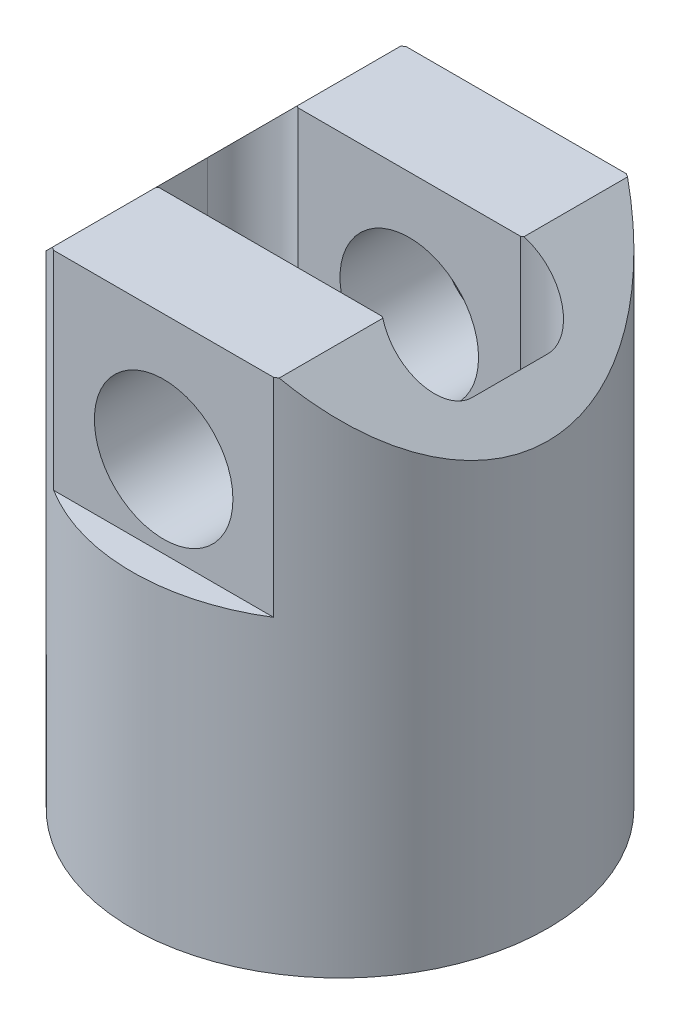
SolidWorks part; units mm, degrees
material "Простая углеродистая сталь"
ref_plane "Спереди" through (0, 0, 0) normal (0, 0, 1) x (1, 0, 0)
ref_plane "Сверху" through (0, 0, 0) normal (0, 1, 0) x (1, 0, 0)
ref_plane "Справа" through (0, 0, 0) normal (1, 0, 0) x (0, 0, -1)
sketch "Эскиз1" plane through (0, 0, 0) normal (0, 0, 1) x (1, 0, 0)
  line L0 (0, 0) -> (0, 118.6898) construction
  line L2 (-33, 0) -> (-33, 82)
  line L3 (-33, 82) -> (0, 82)
  line L4 (0, 82) -> (0, 40)
  line L5 (0, 40) -> (-22.5, 40)
  line L6 (-22.5, 40) -> (-22.5, 37)
  line L7 (-22.5, 37) -> (-27.25, 37)
  line L8 (-28.25, 36) -> (-28.25, 29.4142)
  line L9 (-27.9571, 28.7071) -> (0, 0.75)
  line L10 (0, 0.75) -> (0, 0)
  line L11 (0, 0) -> (-33, 0)
  arc A0 (-28.25, 29.4142) -> (-27.9571, 28.7071) centre (-27.25, 29.4142) ccw
  arc A1 (-27.25, 37) -> (-28.25, 36) centre (-27.25, 36) ccw
  point P14 (-28.25, 29)
  point P17 (-28.25, 37)
  dimension "D9" = 1
  dimension "D1" = 66
  dimension "H" = 82
  dimension "D3" = 45
  dimension "D4" = 56.5
  dimension "D7" = 8
  dimension "D8" = 45
  dimension "h1" = 40
  dimension "h2" = 37
revolve "Повернуть1" add sketch "Эскиз1" angle 360 about L0
hole_wizard "Отверстие обработанное метчиком M561" positions "Эскиз3" profile "Эскиз2" tap size "M56" standard "ISO"
sketch "Эскиз3" plane through (0, 0, 0) normal (0, -1, 0) x (-1, 0, 0)
  point P0 (0, 0)
sketch "Эскиз2" plane through (0, 0, 0) normal (1, 0, 0) x (0, 0, -1)
  line L0 (0, 0) -> (0, 30)
  line L1 (0, 30) -> (27, 30)
  line L2 (27, 30) -> (27, 2)
  line L3 (27, 2) -> (29, 0)
  line L5 (29, 0) -> (0, 0)
  line L6 (-27, 2) -> (-29, 0) construction
  line L10 (0, 30) -> (-27, 30) construction
  line L11 (0, -6.35) -> (0, 107.95) construction
  dimension "Диаметр сверла" = 54
  dimension "Глубина сверла" = 30
  dimension "Диаметр передней зенковки" = 58
  dimension "Угол передней зенковки" = 90
  dimension "Угол заточки сверла" = 180
cosmetic thread "Отверстие резьбы2" parameters "D1"=27.75, "D2"=56
sketch "Эскиз4" plane through (0, 0, 0) normal (0, 0, 1) x (1, 0, 0)
  line L0 (33, 82) -> (-33, 82) construction
  line L1 (-33, 49) -> (33, 49)
  line L2 (-33, 49) -> (-33, 82)
  line L3 (-33, 82) -> (33, 82)
  line L4 (33, 49) -> (33, 82)
  line L5 (33, 0) -> (33, 82) construction
  line L6 (-33, 82) -> (-33, 0) construction
  dimension "D1" = 33
extrude "Вырез-Вытянуть1" cut sketch "Эскиз4" along normal through all from offset 28
extrude "Вырез-Вытянуть2" cut sketch "Эскиз4<2>" against normal through all from offset 28 offset against normal yes
sketch "Эскиз4<2>" plane through (0, 0, 0) normal (0, 0, 1) x (1, 0, 0) same geometry as "Эскиз4"
sketch "Эскиз5" plane through (0, 0, 28) normal (0, 0, 1) x (1, 0, 0)
  circle A0 centre (0, 62) radius 11
  dimension "D2" = 22
  dimension "h'" = 62
extrude "Вырез-Вытянуть3" cut sketch "Эскиз5" against normal through all
sketch "Эскиз6" plane through (0, 82, 0) normal (0, 1, 0) x (1, 0, 0)
  line L0 (-27, 0) -> (27, 0) construction
  line L1 (17.6834, -11) -> (-17.6834, -11)
  line L2 (-17.6834, 11) -> (17.6834, 11)
  line L3 (-27, -6) -> (-27, 6)
  line L4 (27, -6) -> (27, 6)
  arc A0 (-17.6834, -11) -> (-27, -6) centre (-21, -6) cw
  arc A1 (-27, 6) -> (-17.6834, 11) centre (-21, 6) cw
  arc A2 (17.6834, -11) -> (27, -6) centre (21, -6) ccw
  arc A3 (27, 6) -> (17.6834, 11) centre (21, 6) ccw
  dimension "D1" = 6
  dimension "D3" = 24
  dimension "D2" = 22
  dimension "D4" = 54
extrude "Вырез-Вытянуть5" cut sketch "Эскиз6" against normal blind 50
sketch "Эскиз7" plane through (0, 0, 0) normal (0, 0, 1) x (1, 0, 0)
  line L0 (-33, 82) -> (-18, 82)
  line L1 (-18, 82) -> (-33, 67)
  line L2 (-33, 82) -> (-33, 0) construction
  line L3 (-33, 67) -> (-33, 82)
  line L4 (0, 0) -> (0, 94.0186) construction
  line L5 (33, 67) -> (33, 82)
  line L6 (18, 82) -> (33, 67)
  line L7 (33, 82) -> (18, 82)
  line L8 (-33, 0) -> (33, 0) construction
  dimension "D1" = 45
  dimension "H 1" = 67
extrude "Вырез-Вытянуть6" cut sketch "Эскиз7" against normal through all and the other way through all
chamfer "Фаска1" distance 1.6 angle 45 1 edges at (-11, 62, -28)
sketch "Эскиз10" plane through (0, 0, 0) normal (0, 0, 1) x (1, 0, 0)
  line L0 (-5.5, 0) -> (5.5, 0)
  line L1 (5.5, 0) -> (5.5, 10.5)
  line L2 (-5.5, 10.5) -> (-5.5, 0)
  arc A0 (5.5, 10.5) -> (-5.5, 10.5) centre (0, 10.5) ccw
  dimension "D1" = 11
  dimension "D2" = 16
extrude "Вырез-Вытянуть8" cut sketch "Эскиз10" against normal through all
